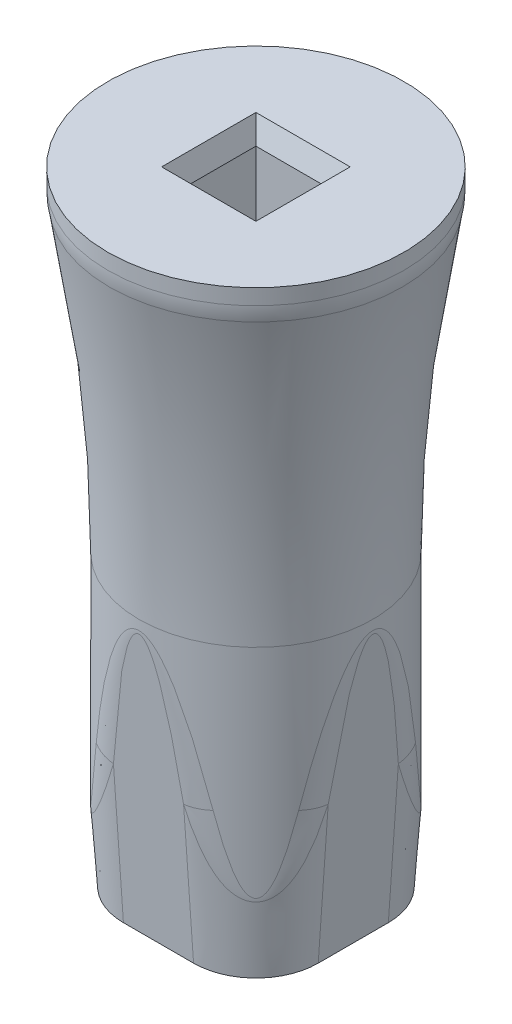
SolidWorks part; units mm, degrees
ref_plane "Спереди" through (0, 0, 0) normal (0, 0, 1) x (1, 0, 0)
ref_plane "Сверху" through (0, 0, 0) normal (0, 1, 0) x (1, 0, 0)
ref_plane "Справа" through (0, 0, 0) normal (1, 0, 0) x (0, 0, -1)
sketch "Эскиз1" plane through (0, 0, 0) normal (0, 1, 0) x (1, 0, 0)
  line L1 (5.05, -5.05) -> (-5.05, -5.05)
  line L2 (5.05, -5.05) -> (5.05, 5.05)
  line L3 (5.05, 5.05) -> (-5.05, 5.05)
  line L4 (-5.05, -5.05) -> (-5.05, 5.05)
  line L5 (5.05, -5.05) -> (-5.05, 5.05) construction
  line L6 (5.05, 5.05) -> (-5.05, -5.05) construction
  circle A0 centre (0, 0) radius 15
  dimension "D1" = 30
  dimension "D2" = 10.1
extrude "Бобышка-Вытянуть1" add sketch "Эскиз1" along normal blind 80
sketch "Sketch1" plane through (0, 80, 0) normal (0, 1, 0) x (1, 0, 0)
  line L1 (5.05, -5.05) -> (-5.05, -5.05)
  line L2 (5.05, -5.05) -> (5.05, 5.05)
  line L3 (5.05, 5.05) -> (-5.05, 5.05)
  line L4 (-5.05, -5.05) -> (-5.05, 5.05)
  line L5 (5.05, -5.05) -> (-5.05, 5.05) construction
  line L6 (5.05, 5.05) -> (-5.05, -5.05) construction
  circle A0 centre (0, 0) radius 19
  dimension "D1" = 38
extrude "Boss-Extrude1" add sketch "Sketch1" against normal blind 3
chamfer "Chamfer1" distance 1 angle 70 4 edges at (5.05, 80, 0) (0, 80, 5.05) (-5.05, 80, 0) (0, 80, -5.05) first distance on face at (0, 80, 0)
fillet "Fillet1" radius 200 1 edges at (0, 77, 15)
fillet "Fillet2" radius 10 1 edges at (0, 77, 19)
sketch "Sketch2" plane through (0, 0, 0) normal (0, -1, 0) x (1, 0, 0)
  line L1 (4.5, 12.5) -> (-4.5, 12.5)
  line L2 (12.5, 4.5) -> (12.5, -4.5)
  line L3 (4.5, -12.5) -> (-4.5, -12.5)
  line L4 (-12.5, 4.5) -> (-12.5, -4.5)
  line L5 (12.5, 12.5) -> (-12.5, -12.5) construction
  line L6 (12.5, -12.5) -> (-12.5, 12.5) construction
  arc A0 (4.5, 12.5) -> (12.5, 4.5) centre (4.5, 4.5) cw
  arc A1 (12.5, -4.5) -> (4.5, -12.5) centre (4.5, -4.5) cw
  arc A2 (-4.5, 12.5) -> (-12.5, 4.5) centre (-4.5, 4.5) ccw
  arc A3 (-12.5, -4.5) -> (-4.5, -12.5) centre (-4.5, -4.5) ccw
  point P0 (0, 0)
  dimension "D2" = 8
  dimension "D1" = 25
extrude "Cut-Extrude1" cut sketch "Sketch2" against normal blind 40 draft 4 flip side to cut
fillet "Fillet6" radius 6 8 edges at (-10.7883, 9.1194, -10.4218) (-15, 35.7517, 0) (-10.4218, 9.1194, 10.7883) (0, 35.7517, 15) (10.7883, 9.1194, 10.4218) (15, 35.7517, 0) (10.4218, 9.1194, -10.7883) (0, 35.7517, -15)
